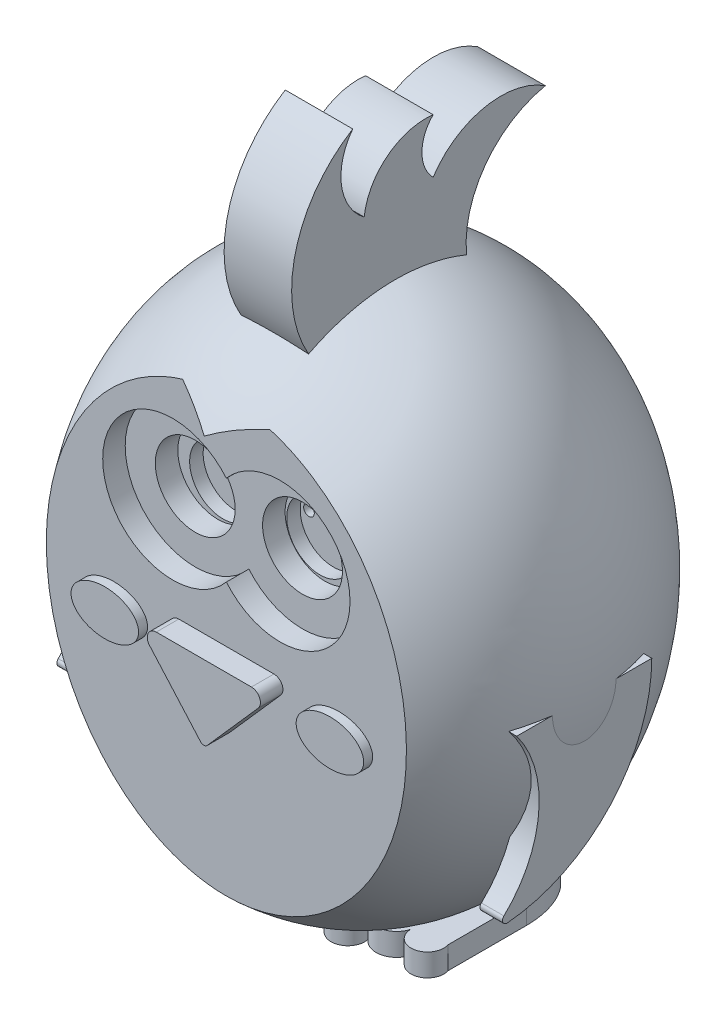
SolidWorks part; units mm, degrees
ref_plane "Front Plane" through (0, 0, 0) normal (0, 0, 1) x (1, 0, 0)
ref_plane "Top Plane" through (0, 0, 0) normal (0, 1, 0) x (1, 0, 0)
ref_plane "Right Plane" through (0, 0, 0) normal (1, 0, 0) x (0, 0, -1)
sketch "Sketch1" plane through (0, 0, 0) normal (0, 0, 1) x (1, 0, 0)
  line L0 (0, 60) -> (0, -60) construction
  line L1 (0, 60) -> (0, -60)
  ellipse E0 centre (0, 0) end of major axis (0, 60) minor radius 50 (0, -60) -> (0, 60) ccw
  dimension "D1" = 50
  dimension "D2" = 120
revolve "Revolve2" add sketch "Sketch1" angle 360 about L0
ref_plane "Plane1" through (0, 0, 50) normal (0, 0, 1) x (1, 0, 0)
sketch "Sketch2" plane through (0, 0, 50) normal (0, 0, 1) x (1, 0, 0)
  line L0 (0, 56.1071) -> (0, -54.0461) construction
  arc A0 (0, 12.4069) -> (0, 32.3665) centre (11.9207, 22.3867) ccw
  circle A2 centre (11.9207, 22.3867) radius 8.8726
  circle A3 centre (10.7795, 21.5461) radius 7.3734
  circle A4 centre (5.3443, 22.3867) radius 1.1887
  arc A5 (10.7795, 28.185) -> (16.0559, 24.9963) centre (11.8234, 23.9524) cw
  arc A6 (10.7795, 27.0255) -> (15.0896, 24.9963) centre (11.92, 23.8558) cw
  arc A7 (10.7795, 28.185) -> (10.7795, 27.0255) centre (10.7795, 27.6052) ccw
  arc A8 (16.0559, 24.9963) -> (15.0896, 24.9963) centre (15.5728, 25.4794) cw
  arc A9 (-10.7795, 28.185) -> (-10.7795, 27.0255) centre (-10.7795, 27.6052) cw
  arc A10 (-16.0559, 24.9963) -> (-15.0896, 24.9963) centre (-15.5728, 25.4794) ccw
  arc A11 (-10.7795, 28.185) -> (-16.0559, 24.9963) centre (-11.8234, 23.9524) ccw
  arc A12 (-10.7795, 27.0255) -> (-15.0896, 24.9963) centre (-11.92, 23.8558) ccw
  circle A13 centre (-5.3443, 22.3867) radius 1.1887
  circle A14 centre (-10.7795, 21.5461) radius 7.3734
  circle A15 centre (-11.9207, 22.3867) radius 8.8726
  arc A16 (0, 12.4069) -> (0, 32.3665) centre (-11.9207, 22.3867) cw
  arc A17 (41.2852, 22.3867) -> (0, -54.0461) centre (-17.5739, 4.8129) cw
  arc A18 (0, 42.9497) -> (41.2852, 22.3867) centre (14.1814, 19.696) cw
  arc A19 (-41.2852, 22.3867) -> (0, -54.0461) centre (17.5739, 4.8129) ccw
  arc A20 (0, 42.9497) -> (-41.2852, 22.3867) centre (-14.1814, 19.696) ccw
  point P40 (0, 0)
extrude "Cut-Extrude2" cut sketch "Sketch2" against normal blind 20 contours A20 A19 A17 A18
extrude "Cut-Extrude3" cut sketch "Sketch2<7>" against normal blind 25 contours L0 A16 A15 | A0 L0 A2 region at (27.0525, 22.3867, 50) region at (-0.4149, 22.3867, 50)
sketch "Sketch2<7>" plane through (0, 0, 50) normal (0, 0, 1) x (1, 0, 0) same geometry as "Sketch2"
extrude "Cut-Extrude5" cut sketch "Sketch2<9>" against normal blind 30 contours A3 A4 A5 A8 A6 A7 | A2 A3 | A15 A14 | A14 A9 A12 A10 A11 A13 region at (3.299, 22.3867, 50) region at (10.8226, 21.2863, 50) region at (-10.8226, 21.2863, 50) region at (-20.5424, 22.3867, 50)
sketch "Sketch2<9>" plane through (0, 0, 50) normal (0, 0, 1) x (1, 0, 0) same geometry as "Sketch2"
extrude "Cut-Extrude6" cut sketch "Sketch2<10>" against normal blind 33 contours A14 A9 A12 A10 A11 A13 | A3 A4 A5 A8 A6 A7 region at (10.8226, 21.2863, 50) region at (-10.8226, 21.2863, 50)
sketch "Sketch2<10>" plane through (0, 0, 50) normal (0, 0, 1) x (1, 0, 0) same geometry as "Sketch2"
extrude "Cut-Extrude7" cut sketch "Sketch2<11>" against normal blind 35 contours A12 A10 A11 A9 | A13 | A4 | A6 A8 A5 A7
sketch "Sketch2<11>" plane through (0, 0, 50) normal (0, 0, 1) x (1, 0, 0) same geometry as "Sketch2"
ref_plane "Plane2" through (0, 0, 10) normal (0, 0, 1) x (1, 0, 0)
sketch "Sketch6" plane through (0, 0, 10) normal (0, 0, 1) x (1, 0, 0)
  line L0 (0, 10.1479) -> (0, -33.502) construction
  line L1 (-10.5681, 0) -> (10.5681, 0)
  line L2 (-12.0677, -3.3232) -> (-0.7498, -16.1502)
  line L3 (12.0677, -3.3232) -> (0.7498, -16.1502)
  arc A0 (-12.0677, -3.3232) -> (-10.5681, 0) centre (-10.5681, -2) cw
  arc A1 (12.0677, -3.3232) -> (10.5681, 0) centre (10.5681, -2) ccw
  arc A3 (-0.7498, -16.1502) -> (0.7498, -16.1502) centre (0, -15.4886) ccw
  point P8 (-15, 0)
  point P12 (0, 0)
  point P17 (0, -17)
  dimension "D3" = 2
  dimension "D4" = 1
  dimension "D1" = 15
  dimension "D2" = 17
extrude "Boss-Extrude2" add sketch "Sketch6" along normal blind 25
ref_plane "Plane3" through (0, -60, 0) normal (0, -1, 0) x (-1, 0, 0)
sketch "Sketch7" plane through (0, -60, 0) normal (0, -1, 0) x (-1, 0, 0)
  line L0 (0, 53.1723) -> (0, -50.1604) construction
  line L1 (24.4937, 12.1636) -> (24.4937, -5.213)
  line L2 (5.5063, 12.1636) -> (5.5063, -5.213)
  line L3 (-5.5063, 12.1636) -> (-5.5063, -5.213)
  line L4 (-24.4937, 12.1636) -> (-24.4937, -5.213)
  arc A0 (24.4937, -5.213) -> (17.3654, -6.4675) centre (21.0184, -6.345) cw
  arc A1 (17.3654, -6.4675) -> (9.5957, -8.1541) centre (13.0251, -5.213) cw
  arc A2 (9.5957, -8.1541) -> (5.5063, -5.213) centre (5.9362, -8.9287) cw
  arc A3 (-24.4937, -5.213) -> (-17.3654, -6.4675) centre (-21.0184, -6.345) ccw
  arc A4 (-9.5957, -8.1541) -> (-5.5063, -5.213) centre (-5.9362, -8.9287) ccw
  arc A5 (-17.3654, -6.4675) -> (-9.5957, -8.1541) centre (-13.0251, -5.213) ccw
  ellipse E0 centre (15, 12.1636) end of major axis (15, 26.4041) minor radius 9.4937 (24.4937, 12.1636) -> (5.5063, 12.1636) ccw
  ellipse E1 centre (-15, 12.1636) end of major axis (-15, -2.0769) minor radius 9.4937 (-24.4937, 12.1636) -> (-5.5063, 12.1636) cw
  point P35 (0, 0)
  point P36 (0, 0)
  dimension "D1" = 30
extrude "Boss-Extrude6" add sketch "Sketch7" along normal mid plane 5 separate body
ref_plane "Plane4" through (47, 0, 0) normal (1, 0, 0) x (0, 0, -1)
sketch "Sketch8" plane through (47, 0, 0) normal (1, 0, 0) x (0, 0, -1)
  line L0 (0, 44.8703) -> (0, -44.5321) construction
  line L1 (15, 0) -> (-15, 0)
  arc A0 (15, 0) -> (-17.0754, -34.8776) centre (-20, 0) cw
  arc A1 (-15, 0) -> (-17.8457, -33.1542) centre (-35.014, -14.9814) cw
  arc A2 (-17.0754, -34.8776) -> (-17.8457, -33.1542) centre (-17.159, -33.8811) cw
  point P6 (0, 0)
  point P11 (-20.0388, -35)
  dimension "D2" = 25
  dimension "D3" = 35
  dimension "D5" = 1
  dimension "D1" = 15
  dimension "D4" = 35
extrude "Boss-Extrude7" add sketch "Sketch8" along normal mid plane 5
mirror "Mirror2" about plane through (0, 0, 0) normal (1, 0, 0) of "Boss-Extrude7"
ref_plane "Plane5" through (0, 0, 27) normal (0, 0, 1) x (1, 0, 0)
sketch "Sketch9" plane through (0, 0, 27) normal (0, 0, 1) x (1, 0, 0)
  line L0 (0, 39.4778) -> (0, -44.2483) construction
  ellipse E0 centre (25, -5) end of major axis (32.5, -5) minor radius 5
  ellipse E1 centre (-25, -5) end of major axis (-32.5, -5) minor radius 5
  dimension "D1" = 10
  dimension "D2" = 15
  dimension "D3" = 25
  dimension "D4" = 5
extrude "Boss-Extrude8" add sketch "Sketch9" along normal blind 5
ref_plane "Plane6" through (0, 0, 0) normal (1, 0, 0) x (0, 0, -1)
sketch "Sketch10" plane through (0, 0, 0) normal (1, 0, 0) x (0, 0, -1)
  line L0 (0, 93.0315) -> (0, -51.0391) construction
  line L1 (16.2053, 53.8849) -> (-18.7947, 53.8849)
  arc A0 (16.2053, 53.8849) -> (33.3503, 79.9608) centre (37.8158, 58.3504) cw
  arc A1 (33.3503, 79.9608) -> (8.4279, 74.811) centre (23.464, 64.9247) ccw
  arc A2 (8.4279, 74.811) -> (8.4279, 86.8484) centre (14.4466, 80.8297) cw
  arc A3 (8.4279, 86.8484) -> (-6.8876, 74.811) centre (6.7889, 73.172) ccw
  arc A4 (-6.8876, 74.811) -> (-9.4251, 93.0315) centre (0.9539, 85.19) cw
  arc A5 (-9.4251, 93.0315) -> (-18.7947, 53.8849) centre (5.4634, 68.7733) ccw
  dimension "D1" = 35
extrude "Boss-Extrude10" add sketch "Sketch10" along normal mid plane 15
